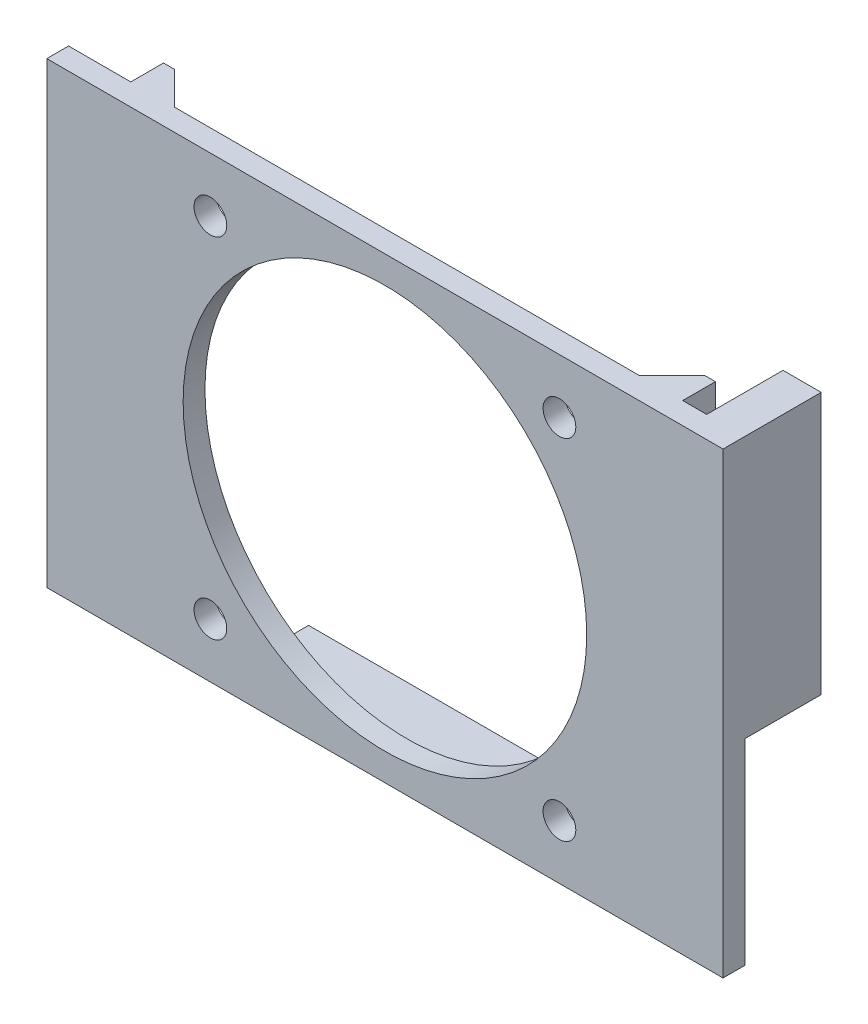
SolidWorks part; units mm, degrees
ref_plane "정면" through (0, 0, 0) normal (0, 0, 1) x (1, 0, 0)
ref_plane "윗면" through (0, 0, 0) normal (0, 1, 0) x (1, 0, 0)
ref_plane "우측면" through (0, 0, 0) normal (1, 0, 0) x (0, 0, -1)
sketch "스케치1" plane through (0, 0, 0) normal (0, 0, 1) x (1, 0, 0)
  line L0 (-31, 21) -> (31, -21) construction
  line L1 (-31, 21) -> (31, 21)
  line L2 (-31, 21) -> (-31, -21)
  line L3 (-31, -21) -> (31, -21)
  line L4 (31, 21) -> (31, -21)
  circle A0 centre (0, 0) radius 18.5
  dimension "D3" = 37
  dimension "D1" = 42
  dimension "D2" = 62
extrude "보스-돌출1" add sketch "스케치1" along normal blind 2
sketch "스케치2" plane through (0, 0, 2) normal (0, 0, 1) x (1, 0, 0)
  line L0 (-16, 16) -> (16, -16) construction
  line L1 (16, -16) -> (16, 16) construction
  line L2 (16, 16) -> (-16, -16) construction
  point P0 (-16, 16)
  point P1 (16, 16)
  point P2 (16, -16)
  point P3 (-16, -16)
  point P8 (0, 0)
  point P9 (0, 0)
  point P11 (0, 0)
  dimension "D1" = 32
  dimension "D2" = 32
hole_wizard "Ø3.0mm 맞춤핀 구멍1" positions "3D스케치1" profile "스케치3" hole size "Ø3.0" standard "Ansi Metric" end condition through all
sketch3d "3D스케치1"
  point P0 (-16, 16, 2)
  point P3 (16, 16, 2)
  point P6 (16, -16, 2)
  point P9 (-16, -16, 2)
sketch "스케치3" plane through (-16, 16, 2) normal (1, 0, 0) x (0, -1, 0)
  line L0 (0, 0) -> (0, 2)
  line L1 (0, 2) -> (1.5, 2)
  line L2 (1.5, 2) -> (1.5, 0)
  line L5 (1.5, 0) -> (0, 0)
  line L11 (0, -6.35) -> (0, 107.95) construction
  dimension "관통 구멍 지름" = 3
  dimension "관통 구멍 깊이" = 2
sketch "스케치4" plane through (0, 0, 0) normal (0, 0, -1) x (-1, 0, 0)
  line L0 (0, 0) -> (0, 25.3922) construction
  line L1 (-31, 21) -> (-27.5, 21)
  line L2 (-31, 21) -> (-31, -3)
  line L3 (-31, -3) -> (-27.5, -3)
  line L4 (-27.5, 21) -> (-27.5, -3)
  line L5 (27.5, 4) -> (31, 4)
  line L6 (27.5, 4) -> (27.5, -21)
  line L7 (27.5, -21) -> (31, -21)
  line L8 (31, 4) -> (31, -21)
  line L9 (31, 21) -> (31, -21) construction
  line L10 (-31, -21) -> (-31, 21) construction
  line L11 (31, -21) -> (-31, -21) construction
  point P11 (-28.6122, 19.0654)
  point P12 (30, 3.3047)
  point P15 (-30, -20.6471)
  point P18 (-30, 21)
  point P20 (25, 3.4741)
  point P21 (0, 0)
  point P22 (-30, -7.9368)
  point P23 (30, -21)
  point P25 (0, 0)
  dimension "D1" = 55
  dimension "D2" = 25
  dimension "D3" = 18
extrude "보스-돌출2" add sketch "스케치4" along normal blind 7
sketch "스케치5" plane through (0, 0, 0) normal (0, 0, -1) x (-1, 0, 0)
  line L0 (0, 0) -> (0, -9.9705) construction
  line L1 (-14, -19) -> (14, -19)
  line L2 (-14, -19) -> (-14, -21)
  line L3 (-14, -21) -> (14, -21)
  line L4 (14, -19) -> (14, -21)
  point P7 (14, -20)
  dimension "D1" = 21
  dimension "D2" = 2
  dimension "D3" = 28
extrude "보스-돌출3" add sketch "스케치5" along normal blind 5
sketch "스케치7" plane through (0, 0, 0) normal (0, 0, -1) x (-1, 0, 0)
  line L0 (-27.5, 21) -> (31, 21) construction
  line L1 (-25.3, 21) -> (-21.3, 21)
  line L2 (-25.3, 21) -> (-25.3, -16)
  line L3 (-25.3, -16) -> (-21.3, -16)
  line L4 (-21.3, 21) -> (-21.3, -16)
  line L5 (0, 0) -> (0, 24.8377) construction
  line L6 (21.3, 21) -> (25.3, 21)
  line L7 (21.3, 21) -> (21.3, -16)
  line L8 (21.3, -16) -> (25.3, -16)
  line L9 (25.3, 21) -> (25.3, -16)
  line L10 (-27.5, -3) -> (-27.5, 21) construction
  line L11 (27.5, -21) -> (14, -21) construction
  dimension "D1" = 2.2
  dimension "D2" = 5
  dimension "D3" = 4
extrude "보스-돌출4" add sketch "스케치7" along normal blind 3
chamfer "모따기1" distance 3 angle 45 2 edges at (-21.3, 2.5, -3) (21.3, 2.5, -3)
